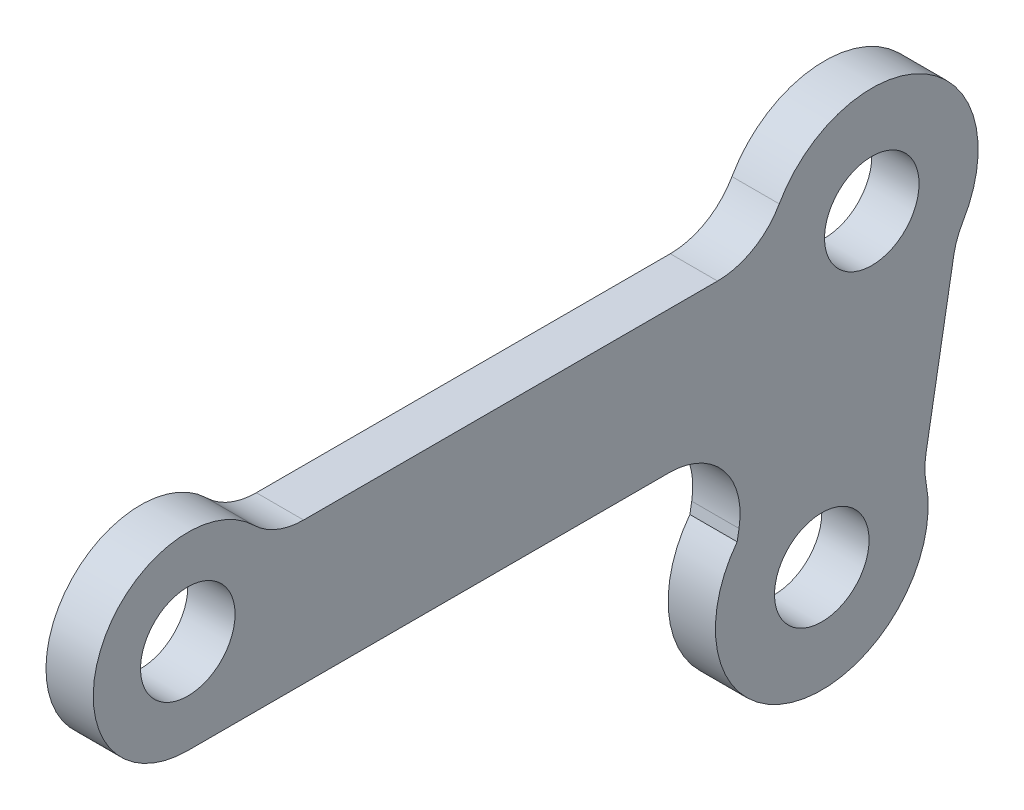
SolidWorks part; units mm, degrees
ref_plane "前视基准面" through (0, 0, 0) normal (0, 0, 1) x (1, 0, 0)
ref_plane "上视基准面" through (0, 0, 0) normal (0, 1, 0) x (1, 0, 0)
ref_plane "右视基准面" through (0, 0, 0) normal (1, 0, 0) x (0, 0, -1)
other "Configuration Table"
sketch "草图1" plane through (0, 0, 0) normal (1, 0, 0) x (0, 0, -1)
  line L1 (-25, 0) -> (0, 0)
  line L2 (-25, 0) -> (-25, -6)
  line L3 (-25, -6) -> (0, -6)
  line L4 (0, 0) -> (0, -6)
  line L5 (0, 0) -> (7.8785, -1.3892)
  line L6 (0, 0) -> (-2.1159, -12)
  line L7 (-2.1159, -12) -> (5.7625, -13.3892)
  line L8 (7.8785, -1.3892) -> (5.7625, -13.3892)
  circle A0 centre (-25, -2) radius 4
  circle A1 centre (3.9392, -0.6946) radius 4.5
  circle A2 centre (1.8233, -12.6946) radius 4.5
  circle A3 centre (-25, -2) radius 2
  circle A4 centre (3.9392, -0.6946) radius 2
  circle A5 centre (1.8233, -12.6946) radius 2
  dimension "D5" = 8
  dimension "D6" = 9
  dimension "D7" = 9
  dimension "D9" = 4
  dimension "D1" = 6
  dimension "D2" = 8
  dimension "D3" = 80
  dimension "D4" = 25
  dimension "D8" = 12
extrude "凸台-拉伸1" add sketch "草图1" along normal blind 2 contours A0 | L1 L4 L3 L2 | A1 | L5 L8 L7 L6 | A2
extrude "切除-拉伸1" cut sketch "草图1<3>" along normal through all contours A3 | A4 | A5
sketch "草图1<3>" plane through (0, 0, 0) normal (1, 0, 0) x (0, 0, -1) same geometry as "草图1"
fillet "圆角1" radius 3 5 edges at (1, -11.359, -6.1205) (1, -3.4194, -7.5205) (1, 0, 0.5068) (1, 0, 21.5359) (1, -6, 1.058)
